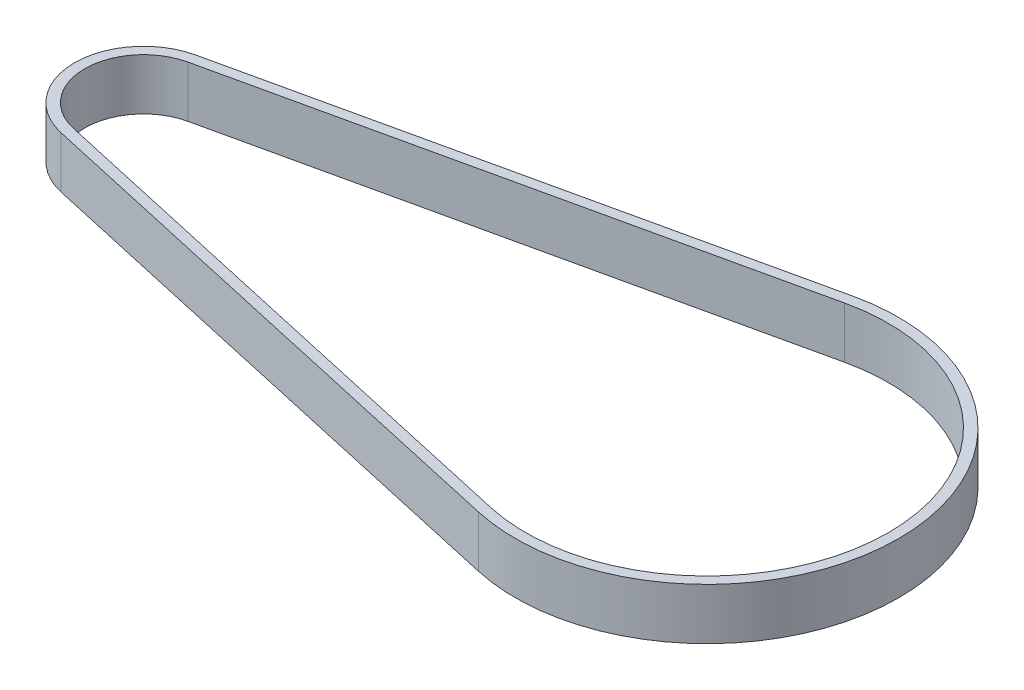
SolidWorks part; units mm, degrees
ref_plane "Ebene vorne" through (0, 0, 0) normal (0, 0, 1) x (1, 0, 0)
ref_plane "Ebene oben" through (0, 0, 0) normal (0, 1, 0) x (1, 0, 0)
ref_plane "Ebene rechts" through (0, 0, 0) normal (1, 0, 0) x (0, 0, -1)
sketch "Skizze1" plane through (0, 0, 0) normal (0, 1, 0) x (1, 0, 0)
  line L0 (-1.0388, 4.6606) -> (40.7837, 13.9819)
  line L1 (-12.3148, 0) -> (45.0363, 0) construction
  line L2 (0, 14.3488) -> (0, -8.3794) construction
  line L3 (-1.0388, -4.6606) -> (40.7837, -13.9819)
  arc A0 (-1.0388, 4.6606) -> (-1.0388, -4.6606) centre (0, 0) ccw
  arc A1 (40.7837, -13.9819) -> (40.7837, 13.9819) centre (43.9, 0) ccw
  dimension "D1" = 9.55
  dimension "D2" = 28.65
  dimension "D3" = 43.9
extrude "Linear-Austragen-Dünn1" add sketch "Skizze1" along normal blind 2 and the other way blind 2 thin thin type two direction wall 0.6 second wall 0.2
ref_axis "Achse1" through (0, -1.65, 0) along (0, 1, 0)
ref_axis "Achse2" through (43.9, -2, 0) along (0, 1, 0)
ref_plane "Ebene1" through (-0.9952, 2, 4.4654) normal (0.9761, 0, 0.2175) x (0.2175, 0, -0.9761)
